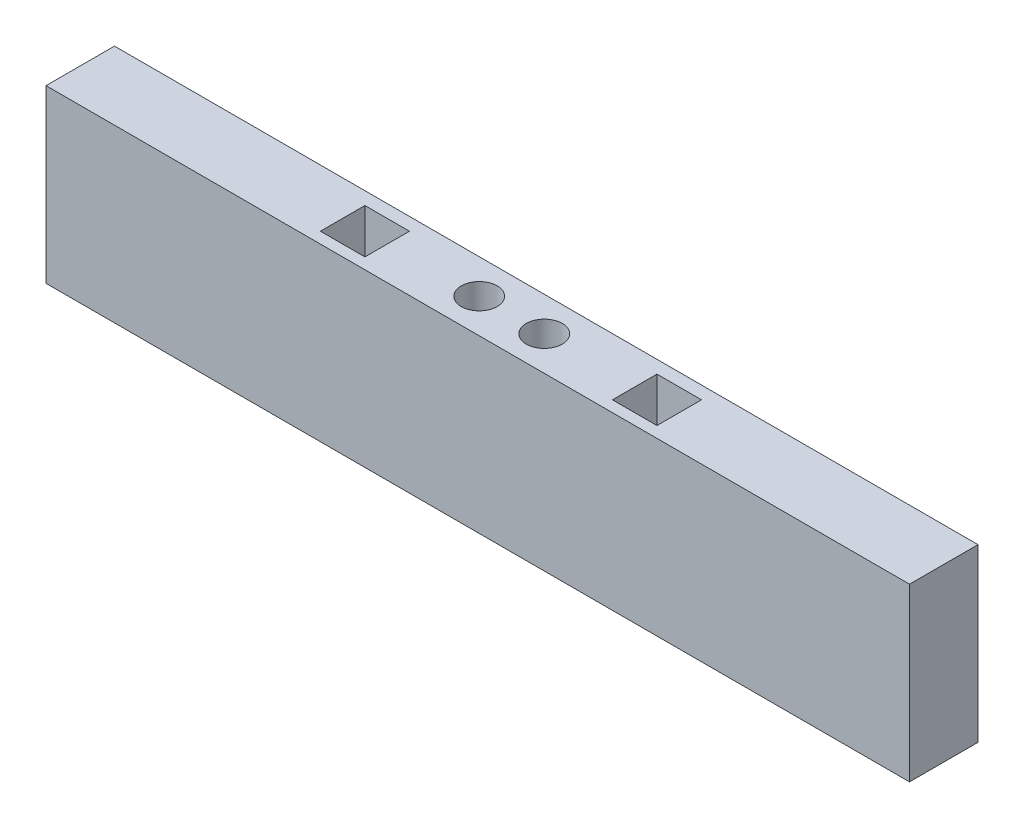
SolidWorks part; units mm, degrees
ref_plane "Front Plane" through (0, 0, 0) normal (0, 0, 1) x (1, 0, 0)
ref_plane "Top Plane" through (0, 0, 0) normal (0, 1, 0) x (1, 0, 0)
ref_plane "Right Plane" through (0, 0, 0) normal (1, 0, 0) x (0, 0, -1)
sketch "Sketch1" plane through (0, 0, 0) normal (0, 0, 1) x (1, 0, 0)
  line L1 (-107.8214, 92.0904) -> (-7.8214, 92.0904)
  line L3 (-107.8214, 44.0904) -> (-7.8214, 44.0904)
  line L5 (-107.8214, 92.0904) -> (-182.8214, 92.0904)
  line L7 (-107.8214, 44.0904) -> (-182.8214, 44.0904)
  line L8 (-182.8214, 92.0904) -> (-182.8214, 44.0904)
  line L9 (-7.8214, 92.0904) -> (117.1786, 92.0904)
  line L11 (-7.8214, 44.0904) -> (117.1786, 44.0904)
  line L12 (117.1786, 92.0904) -> (117.1786, 44.0904)
  dimension "D1" = 48
  dimension "D2" = 100
  dimension "D3" = 75
  dimension "D4" = 125
extrude "Boss-Extrude1" add sketch "Sketch1" along normal blind 20
sketch "Sketch5" plane through (0, 92.0904, 0) normal (0, 1, 0) x (1, 0, 0)
  line L0 (-182.8214, -20) -> (-157.8214, -20) construction
  line L2 (117.1786, -20) -> (-182.8214, -20) construction
  line L3 (-157.8214, -20) -> (-57.8214, -20) construction
  line L4 (-57.8214, -20) -> (-66.3214, -20) construction
  line L5 (-66.3214, -20) -> (-66.3214, -16) construction
  line L6 (-66.3214, -16) -> (-66.3214, -10) construction
  line L7 (-66.3214, -10) -> (-47.3214, -10) construction
  circle A0 centre (-66.3214, -10) radius 5.25
  circle A1 centre (-47.3214, -10) radius 5.25
extrude "Cut-Extrude4" cut sketch "Sketch5" against normal blind 20
sketch "Sketch6" plane through (0, 92.0904, 0) normal (0, 1, 0) x (1, 0, 0)
  line L0 (-182.8214, 0) -> (-105.6914, 0) construction
  line L1 (117.1786, 0) -> (-182.8214, 0) construction
  line L2 (-105.6914, 0) -> (-105.6914, -4) construction
  line L3 (-105.9414, -3.75) -> (-92.9414, -3.75)
  line L8 (-92.9414, -3.75) -> (-92.9414, -16.75)
  line L9 (-105.9414, -16.75) -> (-92.9414, -16.75)
  line L10 (-105.9414, -3.75) -> (-105.9414, -16.75)
extrude "Cut-Extrude5" cut sketch "Sketch6" against normal blind 15.5
sketch "Sketch7" plane through (0, 92.0904, 0) normal (0, 1, 0) x (1, 0, 0)
  line L0 (117.1786, 0) -> (-7.9138, 0) construction
  line L1 (117.1786, 0) -> (-182.8214, 0) construction
  line L2 (-7.9138, 0) -> (-7.9138, -4) construction
  line L3 (-7.6638, -3.75) -> (-20.6638, -3.75)
  line L8 (-20.6638, -3.75) -> (-20.6638, -16.75)
  line L9 (-7.6638, -16.75) -> (-20.6638, -16.75)
  line L10 (-7.6638, -3.75) -> (-7.6638, -16.75)
extrude "Cut-Extrude6" cut sketch "Sketch7" against normal blind 15.5
sketch "Sketch8" plane through (0, 0, 20) normal (0, 0, 1) x (1, 0, 0)
  line L0 (117.1786, 44.0904) -> (117.1786, 92.0904) construction
  line L1 (-182.8214, 44.0904) -> (117.1786, 44.0904)
  line L2 (-182.8214, 44.0904) -> (-182.8214, -57.9096)
  line L3 (-182.8214, -57.9096) -> (117.1786, -57.9096)
  line L4 (117.1786, 44.0904) -> (117.1786, -57.9096)
  dimension "D1" = 150
extrude "Boss-Extrude2" add sketch "Sketch8" against normal up to surface (20 mm away) up to face at (-32.8214, 68.0904, 0)
sketch "Sketch9" plane through (0, 92.0904, 0) normal (0, 1, 0) x (1, 0, 0)
  line L1 (-105.9414, -3.75) -> (-105.9414, -16.75) construction
  line L2 (-7.6638, -3.75) -> (-7.6638, -16.75) construction
  line L4 (117.1786, 0) -> (-182.8214, 0) construction
  line L5 (69.3362, 0) -> (69.3362, -20) construction
  line L6 (117.1786, -20) -> (-182.8214, -20) construction
  line L8 (117.1786, -20) -> (69.3362, -20)
  line L9 (117.1786, -20) -> (117.1786, 0)
  line L10 (117.1786, 0) -> (69.3362, 0)
  line L11 (69.3362, -20) -> (69.3362, 0)
  dimension "D1" = 77
extrude "Cut-Extrude7" cut sketch "Sketch9" against normal up to vertex (150 mm away) up to point (117.1786, -57.9096, 0)
sketch "Sketch10" plane through (0, 0, 0) normal (0, 0, -1) x (-1, 0, 0)
  line L3 (-69.3362, -7.9096) -> (182.8214, -7.9096)
  line L6 (182.8214, 92.0904) -> (182.8214, -57.9096) construction
  line L8 (-69.3362, -57.9096) -> (182.8214, -57.9096)
  line L9 (-69.3362, -57.9096) -> (-69.3362, -7.9096)
  line L11 (182.8214, -57.9096) -> (182.8214, -7.9096)
  dimension "D1" = 50
extrude "Cut-Extrude8" cut sketch "Sketch10" against normal blind 310
sketch "Sketch11" plane through (0, 0, 0) normal (0, 0, -1) x (-1, 0, 0)
  line L1 (-69.3362, -7.9096) -> (182.8214, -7.9096)
  line L2 (-69.3362, -7.9096) -> (-69.3362, 42.0904)
  line L3 (-69.3362, 42.0904) -> (182.8214, 42.0904)
  line L4 (182.8214, -7.9096) -> (182.8214, 42.0904)
extrude "Cut-Extrude9" cut sketch "Sketch11" against normal up to surface (20 mm away) up to face at (-56.7426, 42.0904, 20)
